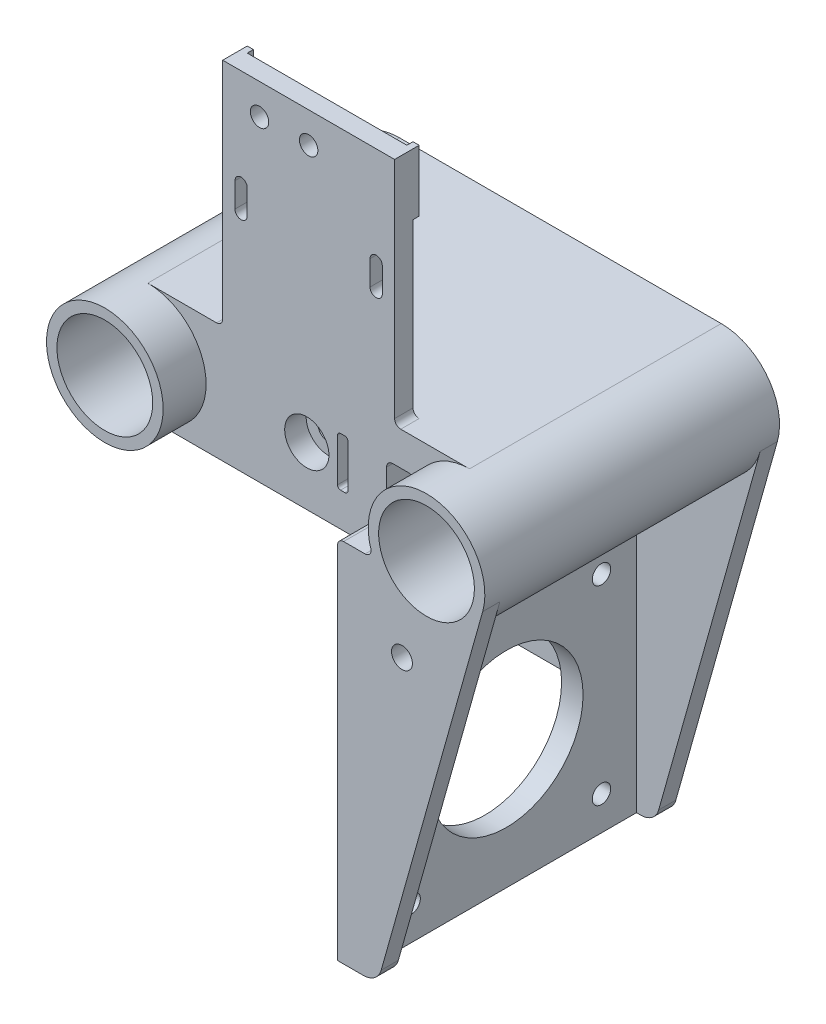
SolidWorks part; units mm, degrees
material "PET"
ref_plane "Front Plane" through (0, 0, 0) normal (0, 0, 1) x (1, 0, 0)
ref_plane "Top Plane" through (0, 0, 0) normal (0, 1, 0) x (1, 0, 0)
ref_plane "Right Plane" through (0, 0, 0) normal (1, 0, 0) x (0, 0, -1)
sketch "Sketch1" plane through (0, 0, 0) normal (0, 0, 1) x (1, 0, 0)
  circle A14 centre (0, 0) radius 7.8
  circle A15 centre (52.4, 0) radius 7.8
  circle A16 centre (0, 0) radius 9.5
  circle A17 centre (52.4, 0) radius 9.5
extrude "Boss-Extrude1" add sketch "Sketch1" along normal blind 48
sketch "Sketch29" plane through (0, 0, 0) normal (0, 0, -1) x (-1, 0, 0)
  line L6 (-52.4, 9.5) -> (0, 9.5)
  line L43 (-38.9, 3) -> (-38.9, -3)
  line L45 (9.5, -36.55) -> (9.5, 0)
  line L46 (-39.9, 4) -> (-42.3861, 4)
  line L47 (-39.9, -4) -> (-42.3861, -4)
  line L66 (-45.0149, -61.4114) -> (-61.5459, -2.5695)
  line L74 (-3.3, -49.35) -> (-31.9, -49.35)
  line L77 (-34.9, -52.35) -> (-34.9, -60.6)
  line L78 (-37.9, -63.6) -> (-42.1267, -63.6)
  arc A2 (-43.3861, 3) -> (-52.4, 9.5) centre (-52.4, 0) ccw
  arc A48 (-38.9, -3) -> (-39.9, -4) centre (-39.9, -3) cw
  arc A50 (-42.3861, 4) -> (-43.3861, 3) centre (-42.3861, 3) ccw
  arc A51 (-39.9, 4) -> (-38.9, 3) centre (-39.9, 3) cw
  circle A58 centre (-3.3, -36.55) radius 1.5
  circle A59 centre (-17.3, -36.55) radius 1.5
  arc A65 (0, 9.5) -> (9.5, 0) centre (0, 0) ccw
  arc A70 (-42.3861, -4) -> (-43.3861, -3) centre (-42.3861, -3) cw
  arc A73 (-42.1267, -63.6) -> (-45.0149, -61.4114) centre (-42.1267, -60.6) cw
  arc A75 (9.5, -36.55) -> (-3.3, -49.35) centre (-3.3, -36.55) cw
  arc A82 (-43.3861, -3) -> (-61.5459, -2.5695) centre (-52.4, 0) cw
  arc A87 (-31.9, -49.35) -> (-34.9, -52.35) centre (-31.9, -52.35) ccw
  arc A88 (-34.9, -60.6) -> (-37.9, -63.6) centre (-37.9, -60.6) cw
extrude "Boss-Extrude18" add sketch "Sketch29" against normal blind 3
sketch "Sketch36" plane through (0, 0, 3) normal (0, 0, 1) x (1, 0, 0)
  line L1 (0, 9.5) -> (52.4, 9.5)
  line L2 (0, -9.5) -> (52.4, -9.5)
  line L3 (38.9, 3) -> (38.9, -3)
  line L4 (39.9, -4) -> (42.3861, -4)
  line L5 (39.9, 4) -> (42.3861, 4)
  line L11 (31.4, 4) -> (32.1, 4)
  line L12 (30.9, 3.5) -> (30.9, -3.5)
  line L13 (31.4, -4) -> (32.1, -4)
  line L14 (32.6, 3.5) -> (32.6, -3.5)
  arc A0 (0, 9.5) -> (0, -9.5) centre (0, 0) cw
  arc A2 (52.4, 9.5) -> (43.3861, 3) centre (52.4, 0) ccw
  arc A4 (39.9, 4) -> (38.9, 3) centre (39.9, 3) ccw
  arc A7 (42.3861, 4) -> (43.3861, 3) centre (42.3861, 3) cw
  arc A8 (42.3861, -4) -> (43.3861, -3) centre (42.3861, -3) ccw
  arc A9 (38.9, -3) -> (39.9, -4) centre (39.9, -3) ccw
  arc A11 (43.3861, -3) -> (52.4, -9.5) centre (52.4, 0) ccw
  arc A20 (32.1, -4) -> (32.6, -3.5) centre (32.1, -3.5) ccw
  arc A21 (30.9, -3.5) -> (31.4, -4) centre (31.4, -3.5) ccw
  arc A22 (32.1, 4) -> (32.6, 3.5) centre (32.1, 3.5) cw
  arc A23 (31.4, 4) -> (30.9, 3.5) centre (31.4, 3.5) ccw
  circle A24 centre (25.9, 0) radius 1.7
extrude "Boss-Extrude26" add sketch "Sketch36" along normal blind 38
sketch "Sketch14" plane through (0, -9.5, 0) normal (0, -1, 0) x (1, 0, 0)
  circle A2 centre (14.4, 28.5) radius 4.125
extrude "Boss-Extrude27" add sketch "Sketch14" along normal blind 4
sketch "Sketch34" plane through (0, 9.5, 0) normal (0, 1, 0) x (1, 0, 0)
  circle A4 centre (14.4, -28.5) radius 6
extrude "Cut-Extrude17" cut sketch "Sketch34" against normal blind 10
sketch "Sketch38" plane through (0, -0.5, 0) normal (0, 1, 0) x (1, 0, 0)
  circle A2 centre (14.5, -28.5) radius 2.15
extrude "Cut-Extrude18" cut sketch "Sketch38" against normal up to surface (13 mm away) up to face at (18.525, -13.5, 28.5)
sketch "Sketch39" plane through (0, 0, 3) normal (0, 0, 1) x (1, 0, 0)
  line L12 (41.4, -63.6) -> (37.9, -63.6)
  line L13 (37.9, -5) -> (37.9, -63.6)
  line L17 (41.4, -63.6) -> (41.4, -9.5)
  line L19 (38.9, -4) -> (42.3861, -4)
  line L20 (41.4, -9.5) -> (52.4, -9.5)
  arc A2 (37.9, -5) -> (38.9, -4) centre (38.9, -5) cw
  arc A3 (42.3861, -4) -> (43.3861, -3) centre (42.3861, -3) ccw
  arc A5 (43.3861, -3) -> (52.4, -9.5) centre (52.4, 0) ccw
extrude "Boss-Extrude43" add sketch "Sketch39" along normal offset from surface (42.2 mm away) 2.8 up to face at (61.9, 0, 48)
sketch "Sketch7" plane through (0, 0, 45.2) normal (0, 0, 1) x (1, 0, 0)
  line L14 (37.9, -63.6) -> (42.1267, -63.6)
  line L19 (45.0149, -61.4114) -> (61.5459, -2.5695)
  line L21 (37.9, -5) -> (37.9, -63.6)
  line L25 (38.9, -4) -> (42.3861, -4)
  circle A4 centre (48.4, -15.6) radius 1.7
  arc A6 (42.1267, -63.6) -> (45.0149, -61.4114) centre (42.1267, -60.6) ccw
  arc A22 (38.9, -4) -> (37.9, -5) centre (38.9, -5) ccw
  arc A28 (43.3861, -3) -> (61.5459, -2.5695) centre (52.4, 0) ccw
  arc A29 (42.3861, -4) -> (43.3861, -3) centre (42.3861, -3) ccw
extrude "Boss-Extrude44" add sketch "Sketch7" along normal up to surface (2.8 mm away) up to face at (61.9, 0, 48)
sketch "Sketch69" plane through (37.9, 0, 0) normal (-1, 0, 0) x (0, 0, 1)
  line L0 (3, -9.5) -> (3, -25)
  line L2 (3, -25) -> (18.5, -9.5)
  line L4 (18.5, -9.5) -> (3, -9.5)
extrude "Boss-Extrude42" add sketch "Sketch69" along normal blind 6.5 from offset 25
sketch "Sketch40" plane through (0, 0, 45.2) normal (0, 0, -1) x (-1, 0, 0)
  line L23 (-42.2, -12.85) -> (-41.4, -12.85)
  line L24 (-42.2, -18.15) -> (-41.4, -18.15)
  line L26 (-41.4, -12.85) -> (-41.4, -18.15)
  line L28 (-42.7, -13.35) -> (-42.7, -17.65)
  arc A10 (-42.2, -12.85) -> (-42.7, -13.35) centre (-42.2, -13.35) ccw
  arc A11 (-42.7, -17.65) -> (-42.2, -18.15) centre (-42.2, -17.65) ccw
extrude "Boss-Extrude45" add sketch "Sketch40" along normal blind 10
sketch "Sketch47" plane through (41.4, 0, 0) normal (1, 0, 0) x (0, 0, -1)
  circle A0 centre (-8.5, -15.55) radius 1.5
  circle A1 centre (-8.5, -15.55) radius 4
extrude "Boss-Extrude40" add sketch "Sketch47" along normal blind 1.4
sketch "Sketch20" plane through (41.4, 0, 0) normal (1, 0, 0) x (0, 0, -1)
  circle A0 centre (-8.5, -58.1) radius 1.5
  circle A1 centre (-39.5, -58.1) radius 1.5
  circle A2 centre (-8.5, -27.1) radius 1.5
  circle A3 centre (-24, -42.6) radius 12.5
  circle A5 centre (-8.5, -15.55) radius 1.5
extrude "Cut-Extrude19" cut sketch "Sketch20" against normal up to surface (3.5 mm away) up to face at (37.9, -26.0333, 30.6667)
sketch "Sketch43" plane through (0, 0, 41) normal (0, 0, 1) x (1, 0, 0)
  circle A1 centre (25.9, 0) radius 3.6
extrude "Cut-Extrude22" cut sketch "Sketch43" against normal blind 3.5
sketch "Sketch59" plane through (0, 0, 41) normal (0, 0, 1) x (1, 0, 0)
  line L20 (11.2, 9.5) -> (41.2, 9.5)
  line L28 (12.2, 10.5) -> (12.2, 47.05)
  line L29 (12.2, 47.05) -> (40.2, 47.05)
  line L30 (40.2, 47.05) -> (40.2, 10.5)
  arc A7 (11.2, 9.5) -> (12.2, 10.5) centre (11.2, 10.5) ccw
  arc A8 (40.2, 10.5) -> (41.2, 9.5) centre (41.2, 10.5) ccw
extrude "Boss-Extrude38" add sketch "Sketch59" against normal blind 3
sketch "Sketch52" plane through (-30, 0, 38) normal (0, 0, -1) x (-1, 0, 0)
  line L9 (-70.2, 47.05) -> (-69.2, 47.05)
  line L10 (-70.2, 47.05) -> (-70.2, 37.05)
  line L11 (-70.2, 37.05) -> (-69.2, 37.05)
  line L12 (-69.2, 47.05) -> (-69.2, 37.05)
  line L13 (-43.2, 47.05) -> (-42.2, 47.05)
  line L14 (-43.2, 47.05) -> (-43.2, 37.05)
  line L15 (-43.2, 37.05) -> (-42.2, 37.05)
  line L16 (-42.2, 47.05) -> (-42.2, 37.05)
extrude "Boss-Extrude36" add sketch "Sketch52" along normal blind 1
sketch "Sketch53" plane through (-30, 0, 38) normal (0, 0, -1) x (-1, 0, 0)
  line L15 (-68.2, 31.05) -> (-68.2, 27.05)
  line L17 (-66.2, 31.05) -> (-66.2, 27.05)
  line L29 (-46.2, 31.05) -> (-46.2, 27.05)
  line L30 (-44.2, 31.05) -> (-44.2, 27.05)
  circle A26 centre (-48.2, 42.05) radius 1.5
  circle A27 centre (-56.2, 42.05) radius 1.5
  arc A32 (-66.2, 31.05) -> (-68.2, 31.05) centre (-67.2, 31.05) ccw
  arc A33 (-68.2, 27.05) -> (-66.2, 27.05) centre (-67.2, 27.05) ccw
  arc A34 (-44.2, 31.05) -> (-46.2, 31.05) centre (-45.2, 31.05) ccw
  arc A35 (-46.2, 27.05) -> (-44.2, 27.05) centre (-45.2, 27.05) ccw
extrude "Cut-Extrude29" cut sketch "Sketch53" against normal up to surface (3 mm away) up to face at (29.5, 0, 41)
sketch "Sketch62" plane through (0, 0, 3) normal (0, 0, 1) x (1, 0, 0)
  line L4 (61.9, -54.1) -> (61.9, 0)
  line L5 (52.4, -63.6) -> (41.4, -63.6)
  line L6 (41.4, -63.6) -> (41.4, -9.5)
  line L7 (41.4, -9.5) -> (52.4, -9.5)
  arc A1 (52.4, -9.5) -> (61.9, 0) centre (52.4, 0) ccw
  arc A2 (52.4, -63.6) -> (61.9, -54.1) centre (52.4, -54.1) ccw
extrude "Cut-Extrude30" cut sketch "Sketch62" against normal blind 0.2
sketch "Sketch70" plane through (0, 0, 0) normal (0, 0, -1) x (-1, 0, 0)
  line L2 (-33.9, -6.5) -> (-22.9, -6.5)
  line L3 (-20.9, -4.5) -> (-20.9, 4.5)
  line L4 (-22.9, 6.5) -> (-33.9, 6.5)
  line L5 (-35.9, 4.5) -> (-35.9, -4.5)
  arc A0 (-35.9, 4.5) -> (-33.9, 6.5) centre (-33.9, 4.5) cw
  arc A2 (-22.9, 6.5) -> (-20.9, 4.5) centre (-22.9, 4.5) cw
  arc A4 (-20.9, -4.5) -> (-22.9, -6.5) centre (-22.9, -4.5) cw
  arc A7 (-33.9, -6.5) -> (-35.9, -4.5) centre (-33.9, -4.5) cw
extrude "Cut-Extrude33" cut sketch "Sketch70" against normal blind 25
sketch "Sketch66" plane through (0, 0, 25) normal (0, 0, -1) x (-1, 0, 0)
  line L1 (-31.4, 4) -> (-32.9, 4)
  line L2 (-30.9, 3.5) -> (-30.9, -3.5)
  line L3 (-31.4, -4) -> (-32.9, -4)
  line L4 (-33.4, 3.5) -> (-33.4, -3.5)
  arc A0 (-30.9, -3.5) -> (-31.4, -4) centre (-31.4, -3.5) cw
  arc A1 (-32.9, -4) -> (-33.4, -3.5) centre (-32.9, -3.5) cw
  arc A2 (-32.9, 4) -> (-33.4, 3.5) centre (-32.9, 3.5) ccw
  arc A3 (-31.4, 4) -> (-30.9, 3.5) centre (-31.4, 3.5) cw
extrude "Cut-Extrude32" cut sketch "Sketch66" against normal blind 8
